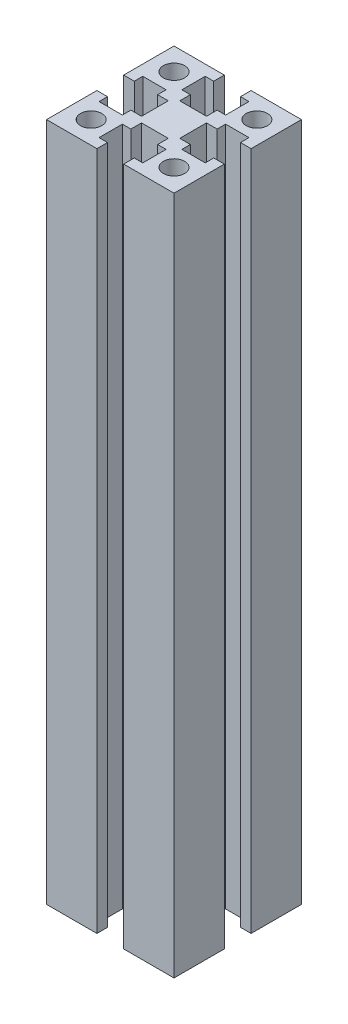
SolidWorks part; units mm, degrees
ref_plane "前视基准面" through (0, 0, 0) normal (0, 0, 1) x (1, 0, 0)
ref_plane "上视基准面" through (0, 0, 0) normal (0, 1, 0) x (1, 0, 0)
ref_plane "右视基准面" through (0, 0, 0) normal (1, 0, 0) x (0, 0, -1)
sketch "草图1" plane through (0, 0, 0) normal (0, 1, 0) x (1, 0, 0)
  line L0 (-15, -3.15) -> (-12.5, -3.15)
  line L1 (-15, 15) -> (-3.15, 15)
  line L2 (-15, 15) -> (-15, 3.15)
  line L3 (-15, -15) -> (-3.15, -15)
  line L4 (15, 15) -> (15, 3.15)
  line L5 (-15, 15) -> (15, -15) construction
  line L6 (-15, -15) -> (15, 15) construction
  line L7 (-12.5, -3.15) -> (-12.5, -5.15)
  line L8 (-12.5, -5.15) -> (-7, -5.15)
  line L9 (-7, -5.15) -> (-7, -3.15)
  line L10 (-7, -3.15) -> (-4.5, -3.15)
  line L11 (-4.5, -3.15) -> (-4.5, 3.15)
  line L12 (-4.5, 3.15) -> (-7, 3.15)
  line L13 (-7, 3.15) -> (-7, 5.15)
  line L14 (-7, 5.15) -> (-12.5, 5.15)
  line L15 (-12.5, 5.15) -> (-12.5, 3.15)
  line L16 (-12.5, 3.15) -> (-15, 3.15)
  line L17 (-15, 0) -> (-4.5, 0) construction
  line L18 (-15, -3.15) -> (-15, -15)
  line L19 (-15, 3.15) -> (-15, 0) construction
  line L20 (-15, 0) -> (-15, -3.15) construction
  line L21 (3.15, 12.5) -> (3.15, 15)
  line L22 (5.15, 12.5) -> (3.15, 12.5)
  line L23 (5.15, 7) -> (5.15, 12.5)
  line L24 (3.15, 7) -> (5.15, 7)
  line L25 (3.15, 4.5) -> (3.15, 7)
  line L26 (-3.15, 4.5) -> (3.15, 4.5)
  line L27 (-3.15, 7) -> (-3.15, 4.5)
  line L28 (-5.15, 7) -> (-3.15, 7)
  line L29 (-5.15, 12.5) -> (-5.15, 7)
  line L30 (-3.15, 12.5) -> (-5.15, 12.5)
  line L31 (-3.15, 15) -> (-3.15, 12.5)
  line L32 (12.5, -3.15) -> (15, -3.15)
  line L33 (12.5, -5.15) -> (12.5, -3.15)
  line L34 (7, -5.15) -> (12.5, -5.15)
  line L35 (7, -3.15) -> (7, -5.15)
  line L36 (4.5, -3.15) -> (7, -3.15)
  line L37 (4.5, 3.15) -> (4.5, -3.15)
  line L38 (7, 3.15) -> (4.5, 3.15)
  line L39 (7, 5.15) -> (7, 3.15)
  line L40 (12.5, 5.15) -> (7, 5.15)
  line L41 (12.5, 3.15) -> (12.5, 5.15)
  line L42 (15, 3.15) -> (12.5, 3.15)
  line L43 (-3.15, -12.5) -> (-3.15, -15)
  line L44 (-5.15, -12.5) -> (-3.15, -12.5)
  line L45 (-5.15, -7) -> (-5.15, -12.5)
  line L46 (-3.15, -7) -> (-5.15, -7)
  line L47 (-3.15, -4.5) -> (-3.15, -7)
  line L48 (3.15, -4.5) -> (-3.15, -4.5)
  line L49 (3.15, -7) -> (3.15, -4.5)
  line L50 (5.15, -7) -> (3.15, -7)
  line L51 (5.15, -12.5) -> (5.15, -7)
  line L52 (3.15, -12.5) -> (5.15, -12.5)
  line L53 (3.15, -15) -> (3.15, -12.5)
  line L54 (3.15, 15) -> (15, 15)
  line L55 (15, -3.15) -> (15, -15)
  line L56 (3.15, -15) -> (15, -15)
  line L57 (-5.15, -9.75) -> (-15, -9.75) construction
  line L58 (-9.75, -5.15) -> (-9.75, -15) construction
  circle A0 centre (-9.75, -9.75) radius 2.5
  circle A1 centre (-9.75, 9.75) radius 2.5
  circle A2 centre (9.75, 9.75) radius 2.5
  circle A3 centre (9.75, -9.75) radius 2.5
  point P0 (0, 0)
  point P59 (0, 0)
  point P72 (0, 0)
  dimension "D1" = 5
  dimension "D2" = 6.3
  dimension "D3" = 10.3
  dimension "D4" = 2.5
  dimension "D5" = 5.5
  dimension "D6" = 10.5
  dimension "D7" = 30
  dimension "D8" = 4
  dimension "D9" = 4
extrude "凸台-拉伸1" add sketch "草图1" along normal mid plane 360
sketch "草图2" plane through (0, 180, 0) normal (0, 1, 0) x (1, 0, 0)
  circle A0 centre (0, 0) radius 82.2505
extrude "切除-拉伸1" cut sketch "草图2" against normal blind 10
sketch "草图3" plane through (0, -180, 0) normal (0, -1, 0) x (1, 0, 0)
  circle A0 centre (0.2164, -1.772) radius 47.3598
extrude "切除-拉伸2" cut sketch "草图3" against normal blind 200
sketch "草图4" plane through (0, 20, 0) normal (0, -1, 0) x (1, 0, 0)
  circle A0 centre (-1.2874, -1.5436) radius 50.0559
extrude "切除-拉伸3" cut sketch "草图4" against normal blind 30
sketch "草图5" plane through (0, 50, 0) normal (0, -1, 0) x (1, 0, 0)
  circle A0 centre (-0.9794, 0.8642) radius 35.7767
extrude "切除-拉伸4" cut sketch "草图5" against normal blind 40
extrude "凸台-拉伸2" add sketch "草图1<3>" along normal blind 200
sketch "草图1<3>" plane through (0, 0, 0) normal (0, 1, 0) x (1, 0, 0) same geometry as "草图1"
sketch "草图6" plane through (0, 200, 0) normal (0, 1, 0) x (1, 0, 0)
  circle A0 centre (-0.6668, 0.5001) radius 45.5084
extrude "切除-拉伸5" cut sketch "草图6" against normal blind 50
sketch "草图7" plane through (0, 150, 0) normal (0, 1, 0) x (1, 0, 0)
  circle A1 centre (0, -1.2412) radius 85.2515
extrude "切除-拉伸7" cut sketch "草图7" against normal blind 20
extrude "凸台-拉伸3" add sketch "草图1<5>" along normal blind 160
sketch "草图1<5>" plane through (0, 0, 0) normal (0, 1, 0) x (1, 0, 0) same geometry as "草图1"
equation "\"零件重量\"= \"SW-质量\" / 1000"
